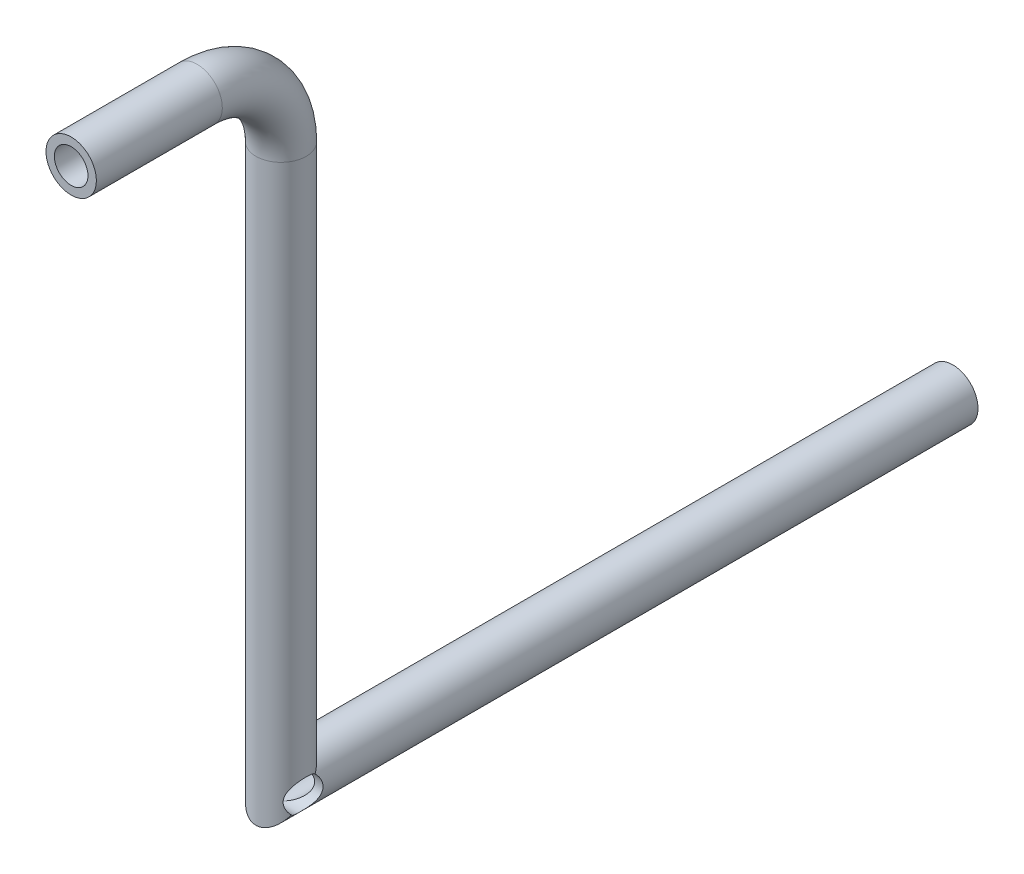
SolidWorks part; units mm, degrees
ref_plane "Front Plane" through (0, 0, 0) normal (0, 0, 1) x (1, 0, 0)
ref_plane "Top Plane" through (0, 0, 0) normal (0, 1, 0) x (1, 0, 0)
ref_plane "Right Plane" through (0, 0, 0) normal (1, 0, 0) x (0, 0, -1)
sketch "Sketch1" plane through (0, 0, 0) normal (1, 0, 0) x (0, 0, -1)
  line L0 (0, 0) -> (150, 0)
  line L1 (250, -100) -> (250, -760)
  line L2 (250, -760) -> (1050, -760)
  arc A0 (150, 0) -> (250, -100) centre (150, -100) cw
  point P7 (250, 0)
  dimension "D4" = 100
  dimension "D1" = 250
  dimension "D2" = 760
  dimension "D3" = 800
sweep "Sweep-Thin1" add path "Sketch1" circular profile diameter 60 parameters "D1"=10, "D3"=60
sketch "Sketch18" plane through (0, 0, 0) normal (1, 0, 0) x (0, 0, -1)
  line L0 (220, -790) -> (280, -730) construction
  circle A0 centre (250, -760) radius 20
  dimension "D1" = 40
extrude "Cut-Extrude1" cut sketch "Sketch18" against normal through all both and the other way through all
ref_plane "Plane1" through (0, 0, -350) normal (0, 0, 1) x (1, 0, 0)
sketch "Sketch19" plane through (0, 0, -350) normal (0, 0, 1) x (1, 0, 0)
  circle A0 centre (0, -285) radius 20
  arc A1 (-26.4575, -774.1421) -> (26.4575, -774.1421) centre (0, -760) ccw construction
  dimension "D2" = 40
  dimension "D1" = 475
extrude "Cut-Extrude2" cut sketch "Sketch19" along normal blind 100
